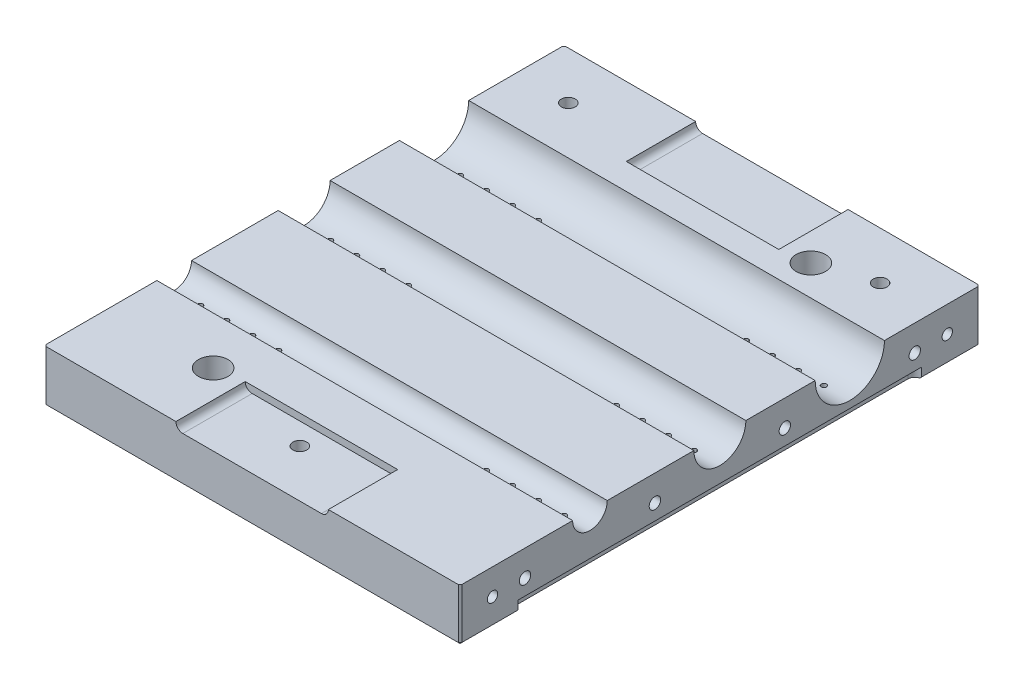
SolidWorks part; units mm, degrees
ref_plane "Front Plane" through (0, 0, 0) normal (0, 0, 1) x (1, 0, 0)
ref_plane "Top Plane" through (0, 0, 0) normal (0, 1, 0) x (1, 0, 0)
ref_plane "Right Plane" through (0, 0, 0) normal (1, 0, 0) x (0, 0, -1)
sketch "Sketch1" plane through (0, 0, 0) normal (0, 1, 0) x (1, 0, 0)
  line L1 (-44.5273, 32.3719) -> (75.4727, 32.3719)
  line L2 (-44.5273, 32.3719) -> (-44.5273, -117.6281)
  line L3 (-44.5273, -117.6281) -> (75.4727, -117.6281)
  line L4 (75.4727, 32.3719) -> (75.4727, -117.6281)
  dimension "D1" = 120
  dimension "D2" = 150
extrude "Boss-Extrude1" add sketch "Sketch1" along normal blind 15
sketch "Sketch2" plane through (75.4727, 0, 0) normal (1, 0, 0) x (0, 0, -1)
  line L0 (-42.6281, 15) -> (-42.6281, 0) construction
  line L1 (-117.6281, 15) -> (32.3719, 15) construction
  line L2 (-117.6281, 0) -> (32.3719, 0) construction
  line L3 (-117.6281, 0) -> (-42.6281, 0) construction
  line L4 (-80.1281, 0) -> (-80.1281, 15) construction
  circle A0 centre (-80.1281, 15) radius 5
  circle A1 centre (-42.6281, 15) radius 7.5
  circle A2 centre (-5.1281, 15) radius 10
  dimension "D1" = 10
  dimension "D2" = 15
  dimension "D3" = 20
extrude "Cut-Extrude1" cut sketch "Sketch2" against normal through all
sketch "Sketch3" plane through (75.4727, 0, 0) normal (1, 0, 0) x (0, 0, -1)
  line L0 (-42.6281, 0) -> (-42.6281, 15) construction
  line L1 (-103.8781, 7.5) -> (-117.6281, 7.5) construction
  line L2 (-103.8781, 15) -> (-103.8781, 0) construction
  line L3 (4.8719, 15) -> (32.3719, 15) construction
  line L4 (18.6219, 15) -> (18.6219, 0) construction
  line L5 (-117.6281, 0) -> (32.3719, 0) construction
  line L6 (18.6219, 7.5) -> (32.3719, 7.5) construction
  line L8 (32.3719, 15) -> (32.3719, 0) construction
sketch "Sketch5" plane through (0, 15, 0) normal (0, 1, 0) x (1, 0, 0)
  line L0 (75.4727, -103.8781) -> (-44.5273, -103.8781) construction
  line L1 (-44.5273, -85.1281) -> (-44.5273, -117.6281) construction
  line L2 (45.4727, 18.6219) -> (75.4727, 18.6219) construction
  line L3 (-14.5273, 18.6219) -> (-44.5273, 18.6219) construction
  line L4 (-44.5273, 32.3719) -> (-44.5273, 4.8719) construction
  line L5 (15.4727, -103.8781) -> (15.4727, 18.6219) construction
  line L6 (45.4727, 18.6219) -> (45.4727, 32.3719) construction
  line L7 (75.4727, 32.3719) -> (-44.5273, 32.3719) construction
  line L8 (-14.5273, 18.6219) -> (-14.5273, 32.3719) construction
  line L9 (-29.5273, 18.6219) -> (-29.5273, 32.3719) construction
  line L10 (75.4727, 4.8719) -> (75.4727, 32.3719) construction
  line L11 (60.4727, 18.6219) -> (60.4727, 32.3719) construction
sketch "Sketch7" plane through (0, 0, 117.6281) normal (0, 0, 1) x (1, 0, 0)
  line L0 (15.4727, 15) -> (15.4727, 0) construction
  line L1 (-44.5273, 15) -> (75.4727, 15) construction
  line L2 (-44.5273, 0) -> (75.4727, 0) construction
sketch "Sketch8" plane through (0, 15, 0) normal (0, 1, 0) x (1, 0, 0)
  line L0 (15.4727, -117.6281) -> (15.4727, -146.7177) construction
  line L1 (-44.5273, -117.6281) -> (75.4727, -117.6281) construction
ref_plane "Plane1" through (15.4727, 0, 0) normal (1, 0, 0) x (0, 0, -1)
sketch "Sketch9" plane through (0, 15, 0) normal (0, 1, 0) x (1, 0, 0)
  line L0 (35.4727, -117.6281) -> (-4.5273, -117.6281)
  line L1 (-44.5273, -117.6281) -> (75.4727, -117.6281) construction
  line L2 (-4.5273, -117.6281) -> (-4.5273, -97.6281)
  line L3 (-4.5273, -97.6281) -> (35.4727, -97.6281)
  line L5 (15.4727, -117.6281) -> (15.4727, -97.6281) construction
  line L6 (35.4727, -117.6281) -> (35.4727, -97.6281)
  dimension "D1" = 20
  dimension "D2" = 20
  dimension "D3" = 20
extrude "Cut-Extrude2" cut sketch "Sketch9" against normal blind 2 contours L3 L6 L0 L2
sketch "Sketch10" plane through (0, 15, 0) normal (0, 1, 0) x (1, 0, 0)
  line L0 (75.4727, -42.6281) -> (101.4988, -42.6281) construction
ref_plane "Plane2" through (0, 0, 42.6281) normal (0, 0, 1) x (1, 0, 0)
mirror "Mirror2" about plane through (0, 0, 42.6281) normal (0, 0, 1) of "Cut-Extrude2"
sketch "Sketch11" plane through (75.4727, 0, 0) normal (1, 0, 0) x (0, 0, -1)
  line L0 (-61.3781, 15) -> (-61.3781, 0) construction
  line L1 (-80.1281, 15) -> (-80.1281, 0) construction
  line L2 (-117.6281, 0) -> (32.3719, 0) construction
  line L3 (-80.1281, 15) -> (-42.6281, 15) construction
  line L4 (-80.1281, 7.5) -> (-61.3781, 7.5) construction
hole_wizard "M4 Tapped Hole2" positions "3DSketch4" profile "Sketch12" tap size "M4" standard "ISO"
sketch3d "3DSketch4"
  point P0 (75.4727, 7.5, 61.3781)
sketch "Sketch12" plane through (75.4727, 7.5, 61.3781) normal (0, 1, 0) x (0, 0, -1)
  line L0 (0, 0) -> (0, 20.9914)
  line L1 (0, 20.9914) -> (1.65, 20)
  line L2 (1.65, 20) -> (1.65, 0)
  line L5 (1.65, 0) -> (0, 0)
  line L10 (0, 20.9914) -> (-1.65, 20) construction
  line L11 (0, -6.35) -> (0, 107.95) construction
  dimension "Tap Drill Dia." = 3.3
  dimension "Tap Drill Depth" = 20
  dimension "Drill Angle" = 118
cosmetic thread "Hole Thread3" parameters "D1"=15, "D2"=4
mirror "Mirror3" about plane through (0, 0, 42.6281) normal (0, 0, 1) of "M4 Tapped Hole2"
mirror "Mirror4" about plane through (15.4727, 0, 0) normal (1, 0, 0) of "Mirror3"
sketch "Sketch13" plane through (75.4727, 0, 0) normal (1, 0, 0) x (0, 0, -1)
  line L0 (-98.8781, 15) -> (-98.8781, 0) construction
  line L1 (-80.1281, 15) -> (-117.6281, 15) construction
  line L2 (-117.6281, 0) -> (32.3719, 0) construction
  line L3 (-98.8781, 7.5) -> (-61.3781, 7.5) construction
hole_wizard "M4 Tapped Hole3" positions "3DSketch5" profile "Sketch15" tap size "M4" standard "ISO"
sketch3d "3DSketch5"
  point P0 (75.4727, 7.5, 98.8781)
sketch "Sketch15" plane through (75.4727, 7.5, 98.8781) normal (0, 1, 0) x (0, 0, -1)
  line L0 (0, 0) -> (0, 20.9914)
  line L1 (0, 20.9914) -> (1.65, 20)
  line L2 (1.65, 20) -> (1.65, 0)
  line L5 (1.65, 0) -> (0, 0)
  line L10 (0, 20.9914) -> (-1.65, 20) construction
  line L11 (0, -6.35) -> (0, 107.95) construction
  dimension "Tap Drill Dia." = 3.3
  dimension "Tap Drill Depth" = 20
  dimension "Drill Angle" = 118
cosmetic thread "Hole Thread4" parameters "D1"=15, "D2"=4
mirror "Mirror5" about plane through (0, 0, 42.6281) normal (0, 0, 1) of "M4 Tapped Hole3"
mirror "Mirror6" about plane through (15.4727, 0, 0) normal (1, 0, 0) of "Mirror5"
sketch "Sketch16" plane through (0, 15, 0) normal (0, 1, 0) x (1, 0, 0)
  line L0 (67.9727, -5.1281) -> (60.4727, -5.1281) construction
  line L2 (45.4727, -42.6281) -> (60.4727, -42.6281) construction
  line L3 (45.4727, -42.6281) -> (45.4727, 32.3719) construction
  line L4 (60.4727, -42.6281) -> (60.4727, 32.3719) construction
  line L5 (75.4727, 32.3719) -> (35.4727, 32.3719) construction
  line L6 (60.4727, -42.6281) -> (75.4727, -42.6281) construction
  line L7 (52.9727, -42.6281) -> (52.9727, 32.3719) construction
  line L8 (67.9727, -42.6281) -> (67.9727, 32.3719) construction
  line L10 (60.4727, -5.1281) -> (52.9727, -5.1281) construction
  line L11 (52.9727, -5.1281) -> (45.4727, -5.1281) construction
hole_wizard "Ø1.5mm Dowel Hole1" positions "3DSketch8" profile "Sketch19" hole size "Ø1.5" standard "ISO"
sketch3d "3DSketch8"
  point P0 (67.9727, 15, 5.1281)
  point P3 (60.4727, 15, 5.1281)
  point P6 (52.9727, 15, 5.1281)
  point P9 (45.4727, 15, 5.1281)
  point P12 (67.9727, 15, 42.6281)
  point P15 (60.4727, 15, 42.6281)
  point P18 (52.9727, 15, 42.6281)
  point P21 (45.4727, 15, 42.6281)
sketch "Sketch19" plane through (67.9727, 15, 5.1281) normal (1, 0, 0) x (0, 0, 1)
  line L0 (0, 0) -> (0, 25.4506)
  line L1 (0, 25.4506) -> (0.75, 25)
  line L2 (0.75, 25) -> (0.75, 0)
  line L5 (0.75, 0) -> (0, 0)
  line L10 (0, 25.4506) -> (-0.75, 25) construction
  line L11 (0, -6.35) -> (0, 107.95) construction
  dimension "Hole Dia." = 1.5
  dimension "Hole Depth" = 25
  dimension "Drill Angle" = 118
mirror "Mirror7" about plane through (0, 0, 42.6281) normal (0, 0, 1) of "Ø1.5mm Dowel Hole1"
mirror "Mirror8" about plane through (15.4727, 0, 0) normal (1, 0, 0) of "Mirror7"
sketch "Sketch20" plane through (0, 0, 0) normal (0, -1, 0) x (1, 0, 0)
  line L0 (-44.5273, 5.1281) -> (-44.5273, -32.3719) construction
  line L2 (-44.5273, 5.1281) -> (-2.3322, 5.1281) construction
  line L3 (-44.5273, -13.6219) -> (-26.2678, -13.6219) construction
  line L4 (-44.5273, 80.1281) -> (-44.5273, 117.6281) construction
  line L6 (-44.5273, 80.1281) -> (5.5325, 80.1281) construction
  line L7 (-44.5273, 98.8781) -> (5.5325, 98.8781) construction
  line L8 (-44.5273, 98.8781) -> (-44.5273, -13.6219)
  line L9 (-44.5273, -13.6219) -> (-42.5273, -13.6219)
  line L10 (-42.5273, -13.6219) -> (-42.5273, 98.8781)
  line L11 (-42.5273, 98.8781) -> (-44.5273, 98.8781)
  dimension "D1" = 2
extrude "Cut-Extrude3" cut sketch "Sketch20" against normal blind 3 contours L10 L11 L8 L9
mirror "Mirror9" about plane through (15.4727, 0, 0) normal (1, 0, 0) of "Cut-Extrude3"
chamfer "Chamfer1" distance 0.5 angle 45 10 edges at (-44.5273, 0, -22.9969) (-44.5273, 7.5, -32.3719) (15.4727, 0, -32.3719) (75.4727, 7.5, -32.3719) (75.4727, 0, -22.9969) (75.4727, 0, 108.2531) (75.4727, 7.5, 117.6281) (-44.5273, 7.5, 117.6281) (-44.5273, 0, 108.2531) (15.4727, 0, 117.6281)
sketch "Sketch22" plane through (75.4727, 0, 0) normal (1, 0, 0) x (0, 0, -1)
  line L0 (-98.8781, 7.5) -> (-117.6281, 7.5) construction
  line L1 (-117.6281, 15) -> (-117.6281, 0) construction
  line L2 (-108.2531, 7.5) -> (-108.2531, 0.5) construction
  line L3 (31.8719, 0.5) -> (-117.1281, 0.5) construction
hole_wizard "Ø3.0mm Dowel Hole1" positions "3DSketch10" profile "Sketch23" hole size "Ø3.0" standard "ISO"
sketch3d "3DSketch10"
  point P0 (75.4727, 7.5, 108.2531)
sketch "Sketch23" plane through (75.4727, 7.5, 108.2531) normal (0, 1, 0) x (0, 0, -1)
  line L0 (0, 0) -> (0, 25.9013)
  line L1 (0, 25.9013) -> (1.5, 25)
  line L2 (1.5, 25) -> (1.5, 0)
  line L5 (1.5, 0) -> (0, 0)
  line L10 (0, 25.9013) -> (-1.5, 25) construction
  line L11 (0, -6.35) -> (0, 107.95) construction
  dimension "Hole Dia." = 3
  dimension "Hole Depth" = 25
  dimension "Drill Angle" = 118
mirror "Mirror10" about plane through (0, 0, 42.6281) normal (0, 0, 1) of "Ø3.0mm Dowel Hole1"
mirror "Mirror11" about plane through (15.4727, 0, 0) normal (1, 0, 0) of "Mirror10"
sketch "Sketch24" plane through (0, 0, 117.6281) normal (0, 0, 1) x (1, 0, 0)
  line L0 (35.4727, 15) -> (37.4727, 15) construction
  line L1 (35.4727, 15) -> (74.9727, 15) construction
  line L2 (35.4727, 13) -> (35.4727, 15)
  line L3 (35.4727, 15) -> (37.4727, 15)
  arc A0 (35.4727, 13) -> (37.4727, 15) centre (35.4727, 15) ccw
  dimension "D1" = 2
extrude "Cut-Extrude4" cut sketch "Sketch24" against normal blind 20
mirror "Mirror12" about plane through (15.4727, 0, 0) normal (1, 0, 0) of "Cut-Extrude4"
mirror "Mirror13" about plane through (0, 0, 42.6281) normal (0, 0, 1) of "Cut-Extrude4", "Mirror12"
sketch "Sketch25" plane through (0, 0, 0) normal (0, -1, 0) x (1, 0, 0)
  line L0 (75.4727, 98.8781) -> (75.4727, 100.8781) construction
  line L1 (75.4727, 117.1281) -> (75.4727, 98.8781) construction
  line L2 (73.4727, 98.8781) -> (75.4727, 98.8781)
  line L3 (75.4727, 98.8781) -> (75.4727, 100.8781)
  arc A0 (73.4727, 98.8781) -> (75.4727, 100.8781) centre (75.4727, 98.8781) cw
  dimension "D1" = 2
extrude "Cut-Extrude5" cut sketch "Sketch25" against normal blind 3
mirror "Mirror14" about plane through (0, 0, 42.6281) normal (0, 0, 1) of "Cut-Extrude5"
mirror "Mirror15" about plane through (15.4727, 0, 0) normal (1, 0, 0) of "Cut-Extrude5", "Mirror14"
sketch "Sketch26" plane through (0, 0, 0) normal (0, -1, 0) x (1, 0, 0)
  line L9 (-14.5273, 98.8781) -> (19.641, 98.8781) construction
  line L10 (-14.5273, 61.3781) -> (7.0526, 61.3781) construction
  line L12 (15.4727, 23.8781) -> (45.4727, 23.8781) construction
  line L15 (45.4727, -13.6219) -> (75.4727, -13.6219) construction
hole_wizard "M10 Tapped Hole2" positions "3DSketch14" profile "Sketch30" tap size "M10" standard "ISO"
sketch3d "3DSketch14"
  point P0 (45.4727, 0, -13.6219)
  point P3 (-14.5273, 0, 98.8781)
sketch "Sketch30" plane through (45.4727, 0, -13.6219) normal (1, 0, 0) x (0, 0, -1)
  line L0 (0, 0) -> (0, 27.0537)
  line L1 (0, 27.0537) -> (4.25, 24.5)
  line L2 (4.25, 24.5) -> (4.25, 0)
  line L5 (4.25, 0) -> (0, 0)
  line L10 (0, 27.0537) -> (-4.25, 24.5) construction
  line L11 (0, -6.35) -> (0, 107.95) construction
  dimension "Tap Drill Dia." = 8.5
  dimension "Tap Drill Depth" = 24.5
  dimension "Drill Angle" = 118
cosmetic thread "Hole Thread9" parameters "D1"=15, "D2"=10
cosmetic thread "Hole Thread10" parameters "D1"=15, "D2"=10
hole_wizard "Ø4.0mm Dowel Hole1" positions "3DSketch15" profile "Sketch31" hole size "Ø4.0" standard "ISO"
sketch3d "3DSketch15"
  point P0 (60.4727, 15, -18.6219)
  point P3 (-29.5273, 15, -18.6219)
  point P6 (15.4727, 15, 103.8781)
sketch "Sketch31" plane through (60.4727, 15, -18.6219) normal (1, 0, 0) x (0, 0, 1)
  line L0 (0, 0) -> (0, 26.2017)
  line L1 (0, 26.2017) -> (2, 25)
  line L2 (2, 25) -> (2, 0)
  line L5 (2, 0) -> (0, 0)
  line L10 (0, 26.2017) -> (-2, 25) construction
  line L11 (0, -6.35) -> (0, 107.95) construction
  dimension "Hole Dia." = 4
  dimension "Hole Depth" = 25
  dimension "Drill Angle" = 118
